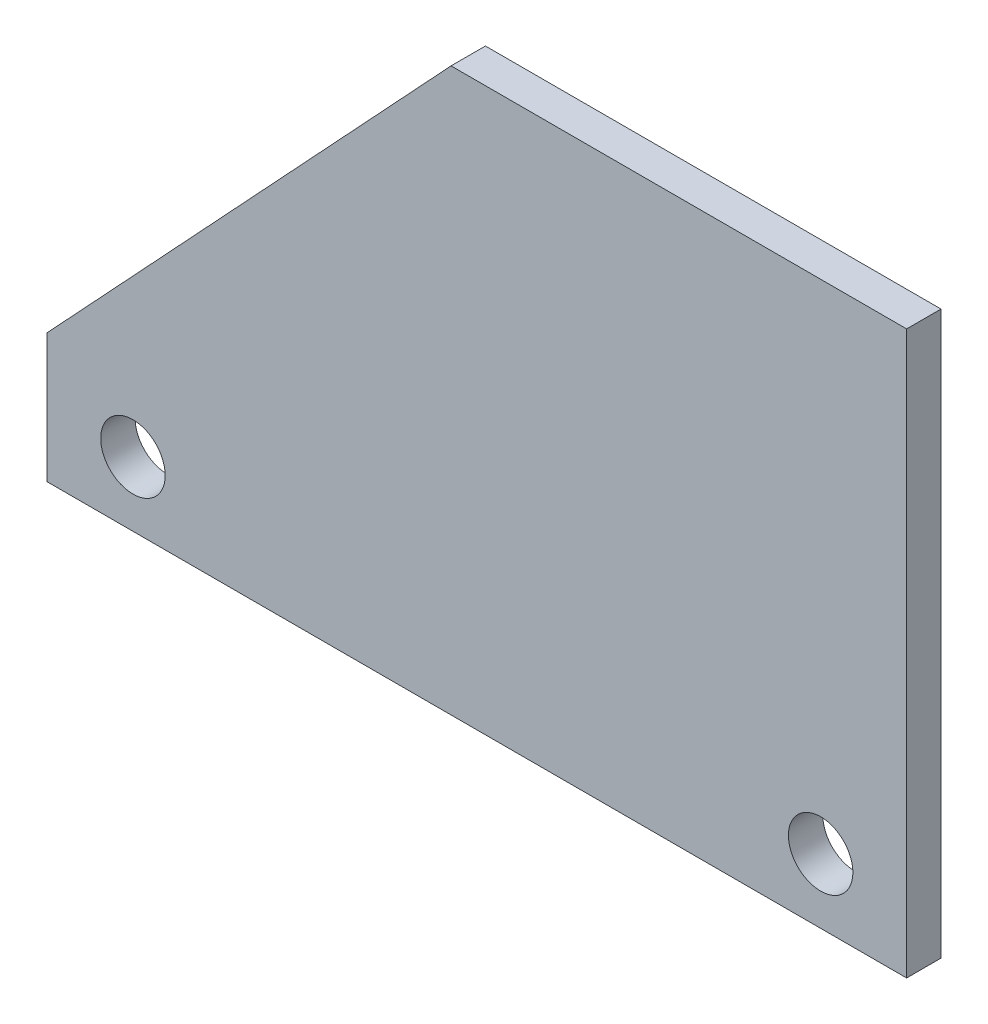
SolidWorks part; units mm, degrees
ref_plane "Front Plane" through (0, 0, 0) normal (0, 0, 1) x (1, 0, 0)
ref_plane "Top Plane" through (0, 0, 0) normal (0, 1, 0) x (1, 0, 0)
ref_plane "Right Plane" through (0, 0, 0) normal (1, 0, 0) x (0, 0, -1)
sketch "Sketch1" plane through (0, 0, 0) normal (0, 0, 1) x (1, 0, 0)
  line L0 (-6.35, 9.525) -> (23.4961, 41.525) construction
  line L1 (23.4961, 41.525) -> (57.15, 41.525) construction
  line L2 (57.15, 41.525) -> (57.15, 0) construction
  line L3 (57.15, 0) -> (44.45, 0) construction
  line L4 (15.1, 9.525) -> (64.1, 9.525)
  line L5 (64.1, 9.525) -> (64.1, 41.025)
  line L6 (64.1, 41.025) -> (15.1, 41.025)
  line L7 (15.1, 41.025) -> (15.1, 9.525)
  line L8 (15.1, 9.525) -> (64.1, 9.525)
  line L9 (64.1, 9.525) -> (64.1, 41.025)
  line L10 (64.1, 41.025) -> (15.1, 41.025)
  line L11 (15.1, 41.025) -> (15.1, 9.525)
  line L12 (44.45, 0) -> (6.35, 0) construction
  line L13 (6.35, 0) -> (-6.35, 0) construction
  line L14 (-6.35, 0) -> (-6.35, 9.525) construction
  line L15 (-6.35, 9.525) -> (23.4961, 41.525)
  line L16 (23.4961, 41.525) -> (57.15, 41.525)
  line L17 (57.15, 41.525) -> (57.15, 0)
  line L18 (57.15, 0) -> (44.45, 0)
  line L19 (44.45, 0) -> (6.35, 0)
  line L20 (6.35, 0) -> (-6.35, 0)
  line L21 (-6.35, 0) -> (-6.35, 9.525)
  circle A0 centre (0, 4.7625) radius 2.3812 construction
  circle A1 centre (50.8, 4.7625) radius 2.3812 construction
  circle A2 centre (0, 4.7625) radius 2.3812
  circle A3 centre (50.8, 4.7625) radius 2.3812
  dimension "D1" = 0
extrude "Boss-Extrude1" add sketch "Sketch1" along normal blind 2.54 contours L15 L16 L17 L18 L19 L20 L21 | A2 | A3
